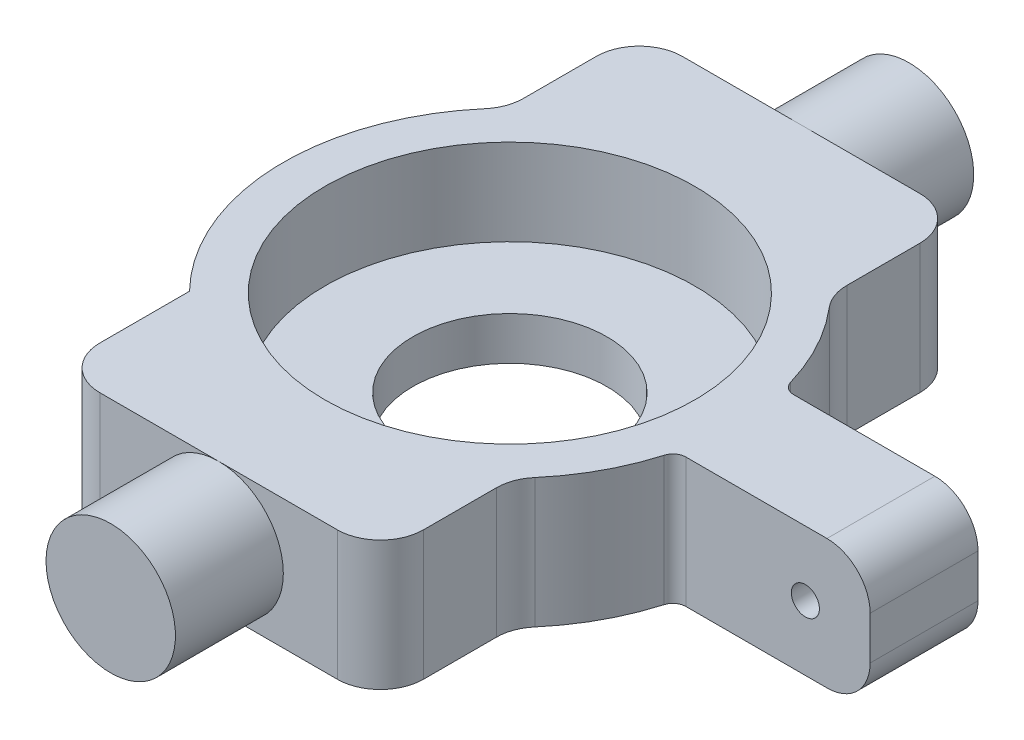
SolidWorks part; units mm, degrees
ref_plane "Front Plane" through (0, 0, 0) normal (0, 0, 1) x (1, 0, 0)
ref_plane "Top Plane" through (0, 0, 0) normal (0, 1, 0) x (1, 0, 0)
ref_plane "Right Plane" through (0, 0, 0) normal (1, 0, 0) x (0, 0, -1)
sketch "Sketch1" plane through (0, 0, 0) normal (0, 1, 0) x (1, 0, 0)
  line L0 (-7.5, 7.3485) -> (-7.5, 13.5)
  line L1 (-7.5, 13.5) -> (7.5, 13.5)
  line L2 (7.5, 13.5) -> (7.5, 7.3485)
  line L3 (0, 13.5) -> (0, 0) construction
  line L4 (0, 0) -> (10.5, 0) construction
  line L5 (-7.5, 13.5) -> (-7.5, 7.3485)
  line L6 (7.5, 7.3485) -> (7.5, 13.5)
  line L7 (7.5, -7.3485) -> (7.5, -13.5)
  line L8 (-7.5, -13.5) -> (-7.5, -7.3485)
  line L9 (7.5, -13.5) -> (7.5, -7.3485)
  line L10 (-7.5, -13.5) -> (7.5, -13.5)
  line L11 (-7.5, -7.3485) -> (-7.5, -13.5)
  circle A0 centre (0, 0) radius 10.5
  circle A1 centre (0, 0) radius 4.5
  dimension "D1" = 27
  dimension "D4" = 9
  dimension "D2" = 15
  dimension "D3" = 3
extrude "Boss-Extrude1" add sketch "Sketch1" along normal blind 6 contours A0 L2 L1 L0 | A0 L8 L10 L7 region at (0, 0, -11.4062) region at (0, 0, 11.4062)
extrude "Boss-Extrude2" add sketch "Sketch1<3>" along normal blind 2 contours A0 region at (0, 0, -10.203)
sketch "Sketch1<3>" plane through (0, 0, 0) normal (0, 1, 0) x (1, 0, 0) same geometry as "Sketch1"
sketch "Sketch2" plane through (0, 2, 0) normal (0, 1, 0) x (1, 0, 0)
  circle A0 centre (0, 0) radius 8.575
  arc A4 (7.5, 7.3485) -> (-7.5, 7.3485) centre (0, 0) ccw
  arc A5 (-7.5, 7.3485) -> (-7.5, -7.3485) centre (0, 0) ccw
  arc A6 (-7.5, -7.3485) -> (7.5, -7.3485) centre (0, 0) ccw
  arc A7 (7.5, -7.3485) -> (7.5, 7.3485) centre (0, 0) ccw
  arc A8 (7.5, 7.3485) -> (-7.5, 7.3485) centre (0, 0) ccw
  arc A9 (-7.5, 7.3485) -> (-7.5, -7.3485) centre (0, 0) ccw
  arc A10 (-7.5, -7.3485) -> (7.5, -7.3485) centre (0, 0) ccw
  arc A11 (7.5, -7.3485) -> (7.5, 7.3485) centre (0, 0) ccw
  dimension "D2" = 17.15
  dimension "D1" = 0
extrude "Boss-Extrude3" add sketch "Sketch2" along normal up to surface (4 mm away) up to face at (0, 6, -11.2121)
sketch "Sketch3" plane through (0, 0, -13.5) normal (0, 0, -1) x (-1, 0, 0)
  line L0 (10.5, 3) -> (-10.5, 3) construction
  line L1 (10.5, 0) -> (10.5, 6) construction
  line L2 (-10.5, 6) -> (-10.5, 0) construction
  circle A0 centre (0, 3) radius 3
  dimension "D1" = 6
extrude "Boss-Extrude4" add sketch "Sketch3" along normal blind 5
mirror "Mirror1" about plane through (0, 0, 0) normal (0, 0, 1) of "Boss-Extrude4"
sketch "Sketch4" plane through (0, 6, 0) normal (0, 1, 0) x (1, 0, 0)
  line L0 (0, 0) -> (10.198, 0) construction
  line L1 (10.198, -2.5) -> (19.198, -2.5)
  line L2 (10.198, -2.5) -> (10.198, 2.5) construction
  line L3 (10.198, 2.5) -> (19.198, 2.5)
  line L4 (19.198, -2.5) -> (19.198, 2.5)
  arc A0 (7.5, -7.3485) -> (7.5, 7.3485) centre (0, 0) ccw construction
  arc A1 (10.198, -2.5) -> (10.198, 2.5) centre (0, 0) ccw
  dimension "D1" = 9
  dimension "D2" = 5
extrude "Boss-Extrude5" add sketch "Sketch4" against normal up to surface (6 mm away) up to face at (0, 0, 0)
sketch "Sketch5" plane through (0, 0, -2.5) normal (0, 0, -1) x (-1, 0, 0)
  line L3 (-19.198, 0) -> (-19.198, 6) construction
  line L4 (-19.198, 3) -> (-10.198, 3) construction
  line L5 (-10.198, 0) -> (-10.198, 6) construction
  circle A2 centre (-16.198, 3) radius 0.65
  dimension "D1" = 3
  dimension "D2" = 1.3
extrude "Cut-Extrude1" cut sketch "Sketch5" against normal up to next
fillet "Fillet1" radius 2 9 edges at (-7.5, 3, -7.3485) (-7.5, 3, -13.5) (7.5, 3, -13.5) (7.5, 3, -7.3485) (7.5, 3, 7.3485) (-7.5, 3, 13.5) (7.5, 3, 13.5) (19.198, 0, 0) (19.198, 6, 0)
fillet "Fillet2" radius 0.6 2 edges at (10.198, 3, -2.5) (10.198, 3, 2.5)
